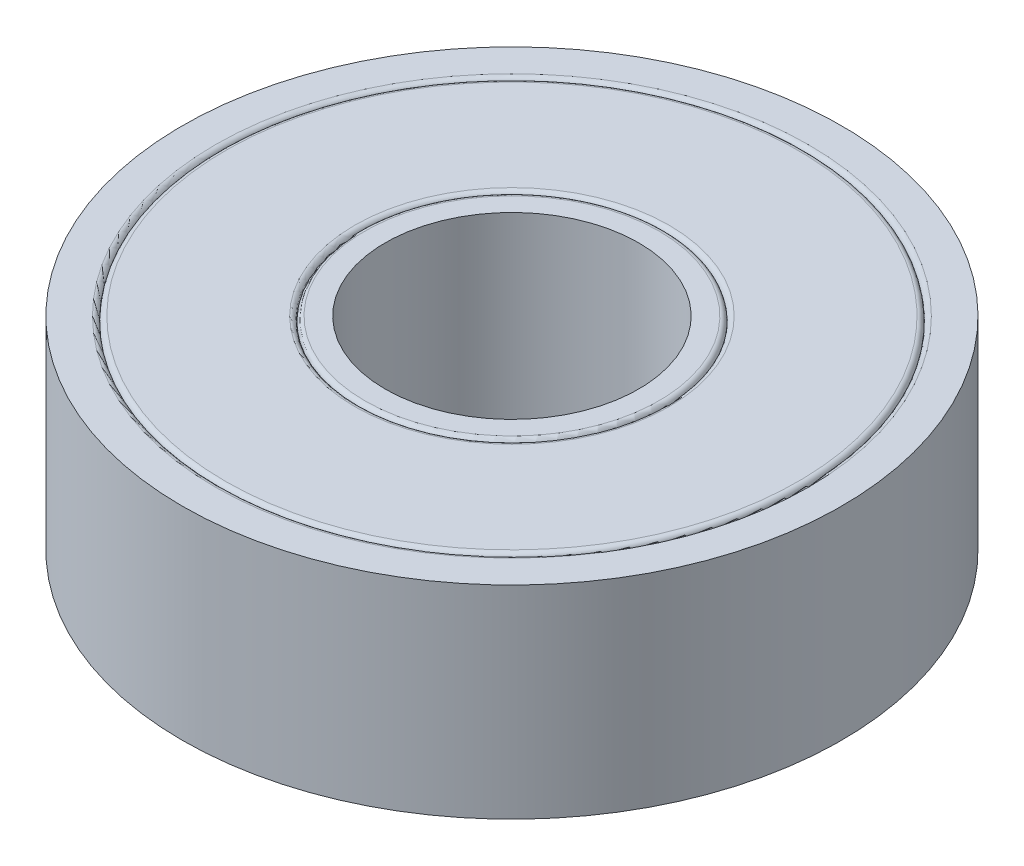
SolidWorks part; units mm, degrees
material "1023 Carbon Steel Sheet (SS)"
ref_plane "Front Plane" through (0, 0, 0) normal (0, 0, 1) x (1, 0, 0)
ref_plane "Top Plane" through (0, 0, 0) normal (0, 1, 0) x (1, 0, 0)
ref_plane "Right Plane" through (0, 0, 0) normal (1, 0, 0) x (0, 0, -1)
sketch "Sketch2" plane through (0, 0, 0) normal (0, 1, 0) x (1, 0, 0)
  circle A0 centre (0, 0) radius 5
  circle A1 centre (0, 0) radius 13
  dimension "D1" = 26
  dimension "D2" = 10
extrude "Boss-Extrude1" add sketch "Sketch2" along normal blind 8
sketch "Sketch1" plane through (0, 8, 0) normal (0, 1, 0) x (1, 0, 0)
  circle A0 centre (0, 0) radius 6
  circle A1 centre (0, 0) radius 11.5
  circle A2 centre (-8.75, 0) radius 2.75
  circle A3 centre (-6.7029, 5.6244) radius 2.75
  circle A4 centre (-1.5194, 8.6171) radius 2.75
  circle A5 centre (4.375, 7.5777) radius 2.75
  circle A6 centre (8.2223, 2.9927) radius 2.75
  circle A7 centre (8.2223, -2.9927) radius 2.75
  circle A8 centre (4.375, -7.5777) radius 2.75
  circle A9 centre (-1.5194, -8.6171) radius 2.75
  circle A10 centre (-6.7029, -5.6244) radius 2.75
  point P26 (0, 0)
  dimension "D1" = 12
  dimension "D2" = 23
  dimension "D3" = 9
extrude "Cut-Extrude2" cut sketch "Sketch1" against normal blind 10 contours A10 A0 A2 A1 | A10 A1 A9 A0 | A9 A1 A8 A0 | A8 A1 A7 A0 | A7 A1 A6 A0 | A6 A1 A5 A0 | A5 A1 A4 A0 | A4 A1 A3 A0 | A3 A1 A2 A0 region at (9.4211, 8, 0) region at (7.217, 8, -6.0558) region at (7.217, 8, 6.0558) region at (1.636, 8, -9.278) region at (1.636, 8, 9.278) region at (-4.7106, 8, -8.1589) region at (-4.7106, 8, 8.1589) region at (-8.8529, 8, -3.2222) region at (-8.8529, 8, 3.2222)
sketch "Sketch4" plane through (0, 8, 0) normal (0, 1, 0) x (1, 0, 0)
  circle A0 centre (0, 0) radius 6
  circle A1 centre (0, 0) radius 11.5
extrude "Cut-Extrude3" cut sketch "Sketch4" against normal blind 1
sketch "Sketch5" plane through (0, 0, 0) normal (0, -1, 0) x (1, 0, 0)
  circle A0 centre (0, 0) radius 6
  circle A1 centre (0, 0) radius 11.5
extrude "Cut-Extrude4" cut sketch "Sketch5" against normal blind 1
fillet "Fillet1" radius 0.2 1 edges at (0, 8, 6)
fillet "Fillet2" radius 0.2 1 edges at (0, 8, 11.5)
sketch "Sketch7" plane through (0, 8, 0) normal (0, 1, 0) x (1, 0, 0)
  circle A0 centre (0, 0) radius 6
  circle A1 centre (0, 0) radius 11.5
  dimension "D1" = 23
  dimension "D2" = 12
extrude "Boss-Extrude2" add sketch "Sketch7" against normal blind 0.5
fillet "Fillet3" radius 0.2 1 edges at (0, 0, 6)
fillet "Fillet4" radius 0.2 1 edges at (0, 0, 11.5)
sketch "Sketch9" plane through (0, 0, 0) normal (0, -1, 0) x (-1, 0, 0)
  circle A0 centre (0, 0) radius 11.5
  circle A1 centre (0, 0) radius 6
  dimension "D1" = 23
  dimension "D2" = 12
extrude "Boss-Extrude3" add sketch "Sketch9" against normal blind 0.5
fillet "Fillet5" radius 0.2 1 edges at (0, 0, -11.5)
fillet "Fillet6" radius 0.2 1 edges at (0, 0, -6)
fillet "Fillet7" radius 0.2 1 edges at (0, 8, 6)
fillet "Fillet8" radius 0.2 1 edges at (0, 8, 11.5)
